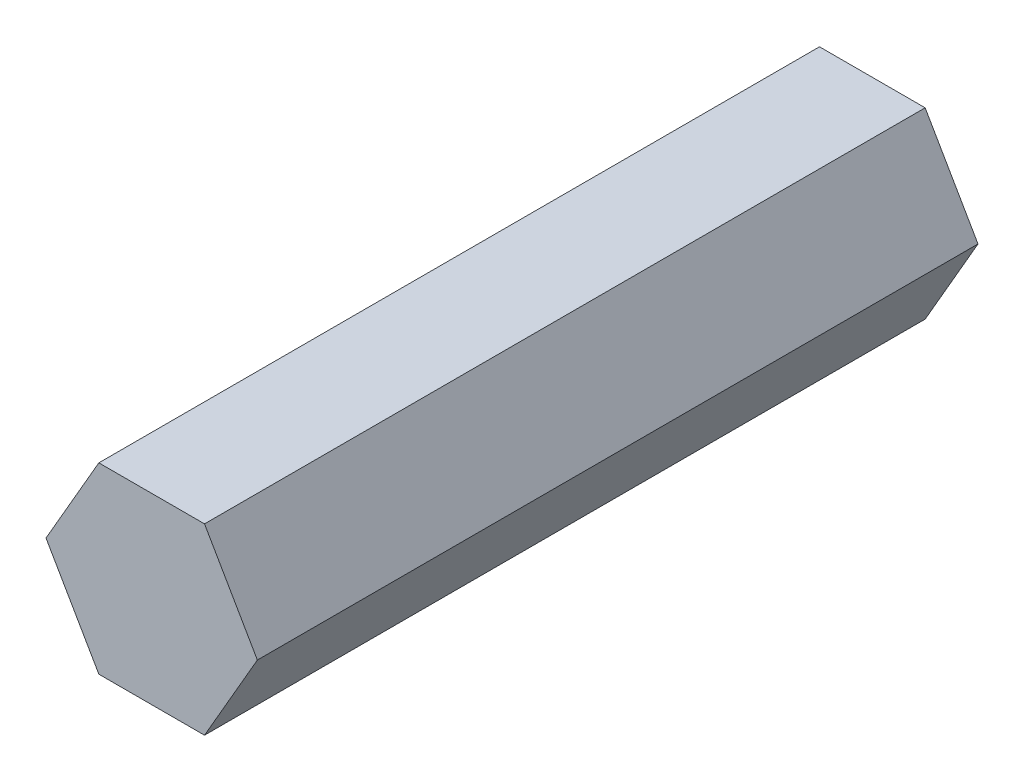
SolidWorks part; units mm, degrees
ref_plane "Front Plane" through (0, 0, 0) normal (0, 0, 1) x (1, 0, 0)
ref_plane "Top Plane" through (0, 0, 0) normal (0, 1, 0) x (1, 0, 0)
ref_plane "Right Plane" through (0, 0, 0) normal (1, 0, 0) x (0, 0, -1)
sketch "Sketch1" plane through (0, 0, 0) normal (0, 0, 1) x (1, 0, 0)
  line L1 (-7.3323, 0) -> (-3.6662, -6.35)
  line L2 (-3.6662, -6.35) -> (3.6662, -6.35)
  line L3 (3.6662, -6.35) -> (7.3323, 0)
  line L4 (7.3323, 0) -> (3.6662, 6.35)
  line L5 (3.6662, 6.35) -> (-3.6662, 6.35)
  line L6 (-3.6662, 6.35) -> (-7.3323, 0)
  circle A0 centre (0, 0) radius 6.35 construction
  dimension "D1" = 12.7
extrude "Boss-Extrude1" add sketch "Sketch1" along normal blind 50 contours L4 L5 L6 L1 L2 L3
